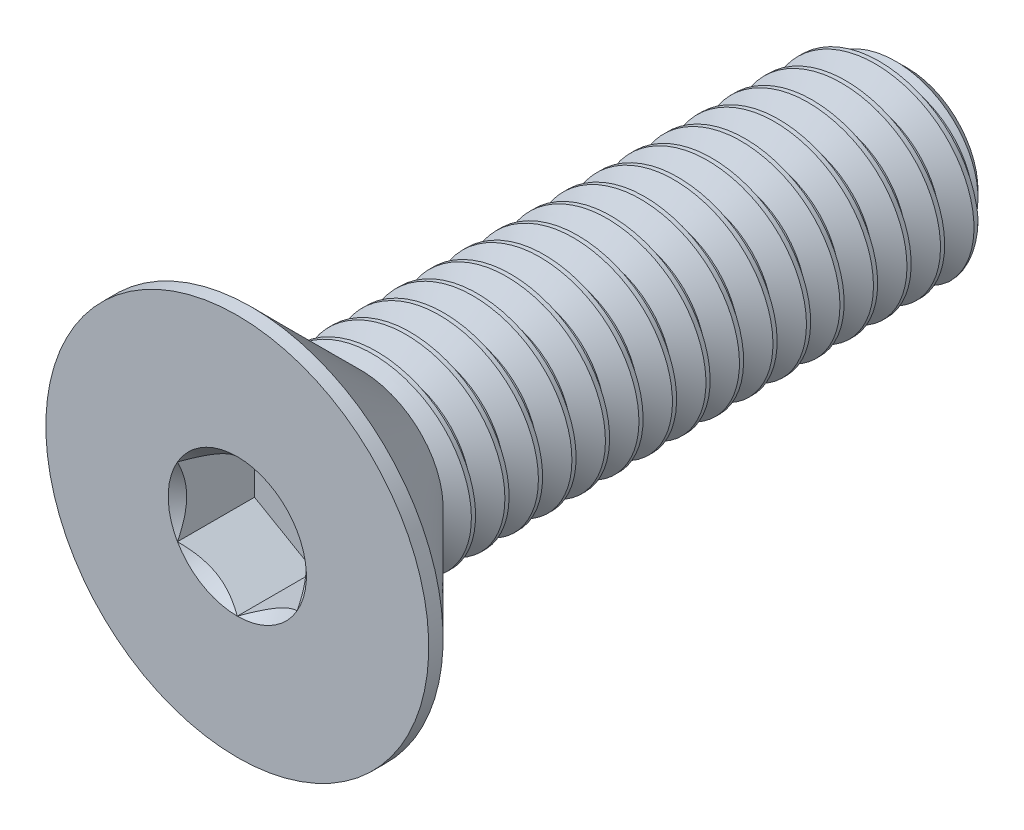
SolidWorks part; units mm, degrees
ref_plane "Front" through (0, 0, 0) normal (0, 0, 1) x (1, 0, 0)
ref_plane "Top" through (0, 0, 0) normal (0, 1, 0) x (1, 0, 0)
ref_plane "Right" through (0, 0, 0) normal (1, 0, 0) x (0, 0, -1)
sketch "Body Sketch" plane through (0, 0, 0) normal (1, 0, 0) x (0, 0, -1)
  line L0 (0, 4) -> (0.3, 4) construction
  line L1 (0.3, 4) -> (2.3, 2) construction
  line L2 (0, 2) -> (14, 2)
  line L3 (14, 2) -> (14, 0)
  line L4 (14, 0) -> (0, 0)
  line L5 (0, 0) -> (0, 4) construction
  line L6 (0, 4) -> (0, -4) construction
  line L7 (14, 2) -> (14, -2) construction
  line L8 (0, -4) -> (0.3, -4) construction
  line L9 (0.3, -4) -> (2.3, -2) construction
  line L11 (0, 2) -> (0, 0)
  line L12 (2.3, 2) -> (2.3, 0) construction
revolve "Body Revolve" add sketch "Body Sketch" angle 360 mid plane about L4
sketch "Sketch3" plane through (0, 0, -14) normal (0, 0, -1) x (-1, 0, 0)
  circle A0 centre (0, 0) radius 2
curve "Helix/Spiral1" pitch 0.7 height 14 radius 2 centre (0, 0, -14) axis (0, 0, 1) start towards (0, 1, 0)
sketch "Sketch2" plane through (0, 0, 0) normal (1, 0, 0) x (0, 0, -1)
  line L0 (14, 2) -> (14.6125, 2)
  line L1 (14.6125, 2) -> (14.35, 1.5453)
  line L2 (14.35, 1.5453) -> (14.2625, 1.5453)
  line L3 (14.2625, 1.5453) -> (14, 2)
  line L4 (14.1312, 1.7727) -> (14.4813, 1.7727) construction
  dimension "D1" = 60
  dimension "D2" = 0.0875
  dimension "D3" = 0.35
chamfer "Chamfer1" distance 0.525 angle 45 1 edges at (0, 2, -14)
sweep "Cut-Sweep1" cut profiles "Sketch2" path "Helix/Spiral1" align with end faces yes
sketch "Sketch7" plane through (0, 0, 0) normal (1, 0, 0) x (0, 0, -1)
  line L0 (0, 4) -> (0.3, 4) construction
  line L1 (0.3, 4) -> (2.3, 2) construction
  line L2 (0, 4) -> (0.3, 4)
  line L3 (0.3, 4) -> (2.3, 2)
  line L4 (2.3, 2) -> (2.3, 0) construction
  line L5 (2.3, 2) -> (2.3, 0)
  line L7 (0, 0) -> (0, 4) construction
  line L8 (0, 0) -> (0, 4)
  line L9 (0, 0) -> (2.3, 0)
  line L10 (4.4, 0) -> (-4.4, 0) construction
revolve "Revolve2" add sketch "Sketch7" angle 360 mid plane about L9
ref_plane "Base of Head Plane" through (0, 0, -2.3) normal (0, 0, 1) x (1, 0, 0)
sketch "Sketch8" plane through (0, 0, -2.3) normal (0, 0, 1) x (1, 0, 0)
  circle A0 centre (0, 0) radius 2
extrude "Boss-Extrude1" add sketch "Sketch8" against normal through all draft 45
sketch "Sketch5" plane through (0, 0, 0) normal (0, 0, 1) x (1, 0, 0)
  line L1 (1.25, -0.7217) -> (1.25, 0.7217)
  line L2 (1.25, 0.7217) -> (0, 1.4434)
  line L3 (0, 1.4434) -> (-1.25, 0.7217)
  line L4 (-1.25, 0.7217) -> (-1.25, -0.7217)
  line L5 (-1.25, -0.7217) -> (0, -1.4434)
  line L6 (0, -1.4434) -> (1.25, -0.7217)
  circle A0 centre (0, 0) radius 1.25 construction
  dimension "Hex" = 2.5
extrude "Cut-Extrude2" cut sketch "Sketch5" against normal blind 1.61
sketch "Sketch6" plane through (0, 0, 0) normal (0, 0, 1) x (1, 0, 0)
  circle A0 centre (0, 0) radius 1.4434
extrude "Cut-Extrude3" cut sketch "Sketch6" against normal blind 1.61 draft 45
equation "\"D3@Helix/Spiral1\" = \"Length@Body Sketch\""
equation "\"D2@Sketch2\" = \"D4@Helix/Spiral1\" * .125"
equation "\"D3@Sketch2\" = \"D4@Helix/Spiral1\" * .5"
equation "\"D1@Chamfer1\" = \"D4@Helix/Spiral1\" * .75"
equation "\"D1@Cut-Extrude2\" = \"Head Ht@Body Sketch\" * .7"
equation "\"D1@Cut-Extrude3\" = \"D1@Cut-Extrude2\""
